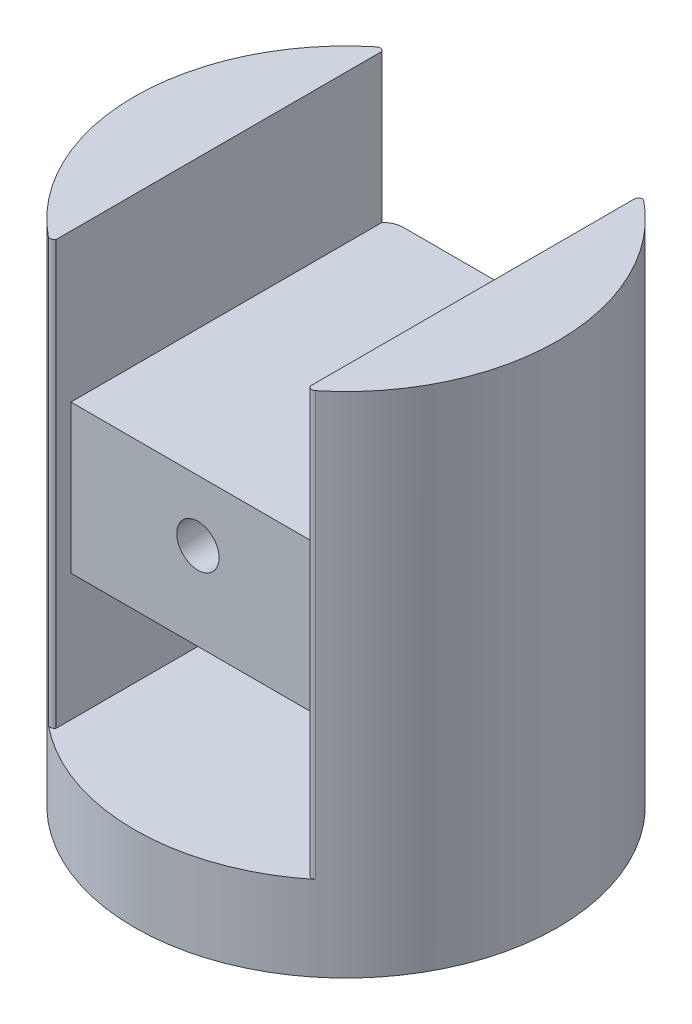
SolidWorks part; units mm, degrees
material "PLA - 20%"
ref_plane "Front Plane" through (0, 0, 0) normal (0, 0, 1) x (1, 0, 0)
ref_plane "Top Plane" through (0, 0, 0) normal (0, 1, 0) x (1, 0, 0)
ref_plane "Right Plane" through (0, 0, 0) normal (1, 0, 0) x (0, 0, -1)
sketch "Sketch1" plane through (0, 0, 0) normal (0, 1, 0) x (1, 0, 0)
  circle A0 centre (0, 0) radius 10
  dimension "D1" = 20
extrude "Boss-Extrude1" add sketch "Sketch1" along normal blind 4
sketch "Sketch2" plane through (0, 4, 0) normal (0, 1, 0) x (1, 0, 0)
  line L0 (-6, 7.7) -> (-6, -7.7)
  line L2 (6, 7.6) -> (6, -7.7)
  arc A1 (6.3151, -7.7536) -> (6.2373, 7.8164) centre (0, 0) ccw
  circle A2 centre (0, 0) radius 10
  arc A3 (-6.3151, 7.7536) -> (-6.3151, -7.7536) centre (0, 0) ccw
  arc A4 (-6, 7.7) -> (-6.3151, 7.7536) centre (-6.1812, 7.5881) ccw
  arc A5 (-6, -7.7) -> (-6.3151, -7.7536) centre (-6.1812, -7.5881) cw
  arc A6 (6, -7.7) -> (6.3151, -7.7536) centre (6.1812, -7.5881) ccw
  arc A7 (6, 7.6) -> (6.2373, 7.8164) centre (6.2137, 7.604) cw
  dimension "D2" = 6
  dimension "D1" = 0
extrude "Boss-Extrude2" add sketch "Sketch2" along normal blind 20
ref_plane "Plane1" through (0, 14, 0) normal (0, 1, 0) x (1, 0, 0)
sketch "Sketch6" plane through (0, 14, 0) normal (0, 1, 0) x (1, 0, 0)
  line L0 (-6, 8) -> (6, 8)
  line L1 (6, 8) -> (6, -7)
  line L3 (6, -7) -> (-6, -7)
  line L4 (-6, -7.7) -> (-6, 7.7) construction
  line L5 (-6, -7) -> (-6, 8)
  dimension "D1" = 15
extrude "Boss-Extrude4" add sketch "Sketch6" along normal blind 3
sketch "Sketch10" plane through (0, 14, 0) normal (0, -1, 0) x (1, 0, 0)
  line L0 (6, -8) -> (-6, -8) construction
  line L1 (-6, 7) -> (6, 7)
  line L2 (-6, 7) -> (-6, -8)
  line L3 (-6, -8) -> (6, -8)
  line L4 (6, 7) -> (6, -8)
  line L5 (6, 7) -> (6, -7.6) construction
extrude "Boss-Extrude5" add sketch "Sketch10" along normal blind 4
fillet "Fillet1" radius 1 2 edges at (6, 13.5, -8) (-6, 13.5, -8)
sketch "Sketch7" plane through (0, 0, 7) normal (0, 0, 1) x (1, 0, 0)
  line L1 (-6, 17) -> (6, 17) construction
  circle A0 centre (0, 14.12) radius 1
  dimension "D1" = 1
  dimension "D2" = 2.88
extrude "Cut-Extrude3" cut sketch "Sketch7" against normal up to next
